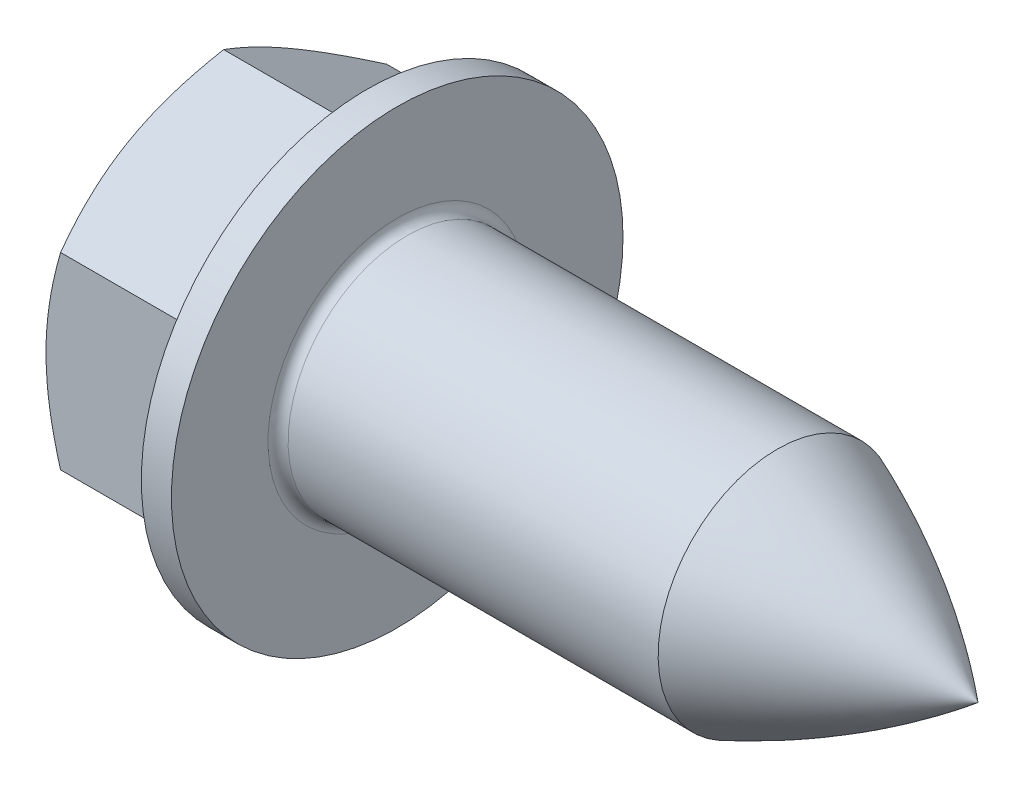
SolidWorks part; units mm, degrees
ref_plane "Front" through (0, 0, 0) normal (0, 0, 1) x (1, 0, 0)
ref_plane "Top" through (0, 0, 0) normal (0, 1, 0) x (1, 0, 0)
ref_plane "Right" through (0, 0, 0) normal (1, 0, 0) x (0, 0, -1)
sketch "Sketch2" plane through (0, 0, 0) normal (1, 0, 0) x (0, 0, -1)
  line L1 (0, 7.5056) -> (-6.5, 3.7528)
  line L2 (-6.5, 3.7528) -> (-6.5, -3.7528)
  line L3 (-6.5, -3.7528) -> (0, -7.5056)
  line L4 (0, -7.5056) -> (6.5, -3.7528)
  line L5 (6.5, -3.7528) -> (6.5, 3.7528)
  line L6 (6.5, 3.7528) -> (0, 7.5056)
  circle A0 centre (0, 0) radius 6.5 construction
extrude "BaseHead" add sketch "Sketch2" along normal blind 7.5
sketch "Sketch1" plane through (0, 0, 0) normal (0, 0, 1) x (1, 0, 0)
  line L0 (-9.5445, 0) -> (41.9665, 0) construction
  line L1 (30.65, 0) -> (30.65, 4.75)
  line L2 (30.65, 4.75) -> (7.5, 4.75)
  line L3 (7.5, 4.75) -> (7.5, 0)
  line L4 (30.65, 0) -> (7.5, 0)
  line L5 (7.5, 3.7528) -> (7.5, -3.7528) construction
  line L6 (9.6, 7.9501) -> (9.6, -3.7754) construction
  dimension "l" = 23.15
revolve "BaseBody" add sketch "Sketch1" angle 360 about L0
cosmetic thread "ThreadCosmetic1" [suppressed] parameters "D1"=21.05, "D2"=8.5
sketch "Sketch3" plane through (7.5, -3.7817, 4.2127) normal (1, 0, 0) x (0, 0, -1)
  circle A0 centre (4.2127, 3.7817) radius 9
  dimension "dc" = 18
extrude "Neck" add sketch "Sketch3" against normal blind 1.2
sketch "Sketch4" plane through (0, 0, 0) normal (0, 0, 1) x (1, 0, 0)
  line L0 (10.6638, 0) -> (-1.5125, 0) construction
  line L2 (0, 6.5) -> (0.5806, 7.5056)
  line L5 (0.5806, 7.5056) -> (0, 7.5056)
  line L6 (0, 7.5056) -> (0, 6.5)
  dimension "D1" = 13
  dimension "D2" = 30
revolve "Cut-Revolve7" cut sketch "Sketch4" angle 360 about L0
fillet "Fillet1" radius 0.4 1 edges at (7.5, 0, 4.75)
fillet "Fillet2" radius 0.6 6 edges at (6.3, -5.6292, -3.25) (6.3, -5.6292, 3.25) (6.3, 0, 6.5) (6.3, 5.6292, 3.25) (6.3, 5.6292, -3.25) (6.3, 0, -6.5)
sketch "Sketch5" plane through (0, 0, 0) normal (0, 0, 1) x (1, 0, 0)
  line L0 (31.9782, 0) -> (17.0112, 0) construction
  line L2 (26.45, -4.75) -> (28.55, -4.75)
  line L3 (28.55, -4.75) -> (30.65, -4.225)
  line L5 (30.65, -4.75) -> (30.65, 4.75) construction
  line L6 (26.45, -4.75) -> (26.45, -5.25)
  line L7 (26.45, -5.25) -> (30.65, -5.25)
  line L8 (30.65, -5.25) -> (30.65, -4.225)
  point P15 (28.55, -4.75)
  dimension "D2" = 2.1
  dimension "D4" = 0.5
  dimension "D1" = 9.5
  dimension "D3" = 0.525
revolve "Cut-Revolve1" cut sketch "Sketch5" angle 360 about L0
sketch "Sketch6" plane through (0, 0, 0) normal (0, 0, 1) x (1, 0, 0)
  line L0 (33.3907, 0) -> (10.0621, 0) construction
  line L2 (30.65, -4.75) -> (30.65, 4.75) construction
  line L3 (30.65, 0) -> (22.65, -4.75) construction
  line L6 (30.65, 0) -> (31.15, 0)
  line L7 (22.65, -4.75) -> (30.65, -4.75)
  line L8 (31.15, 0) -> (31.15, -4.75)
  line L9 (31.15, -4.75) -> (30.65, -4.75)
  arc A0 (30.65, 0) -> (22.65, -4.75) centre (10.4863, 24.8481) cw
  dimension "D1" = 32
  dimension "D3" = 9.5
  dimension "D2" = 0.5
revolve "Cut-Revolve6" cut sketch "Sketch6" angle 360 about L0
sketch "Sketch7" plane through (0, 0, 0) normal (0, 0, 1) x (1, 0, 0)
  line L0 (0, 0) -> (-5.4653, 0) construction
  line L1 (-0.1, 5.4167) -> (0.9, 5.4167)
  line L2 (-0.1, 5.4167) -> (-0.1, 0)
  line L3 (-0.1, 0) -> (1.15, 0)
  line L4 (1.15, 5.1667) -> (1.15, 0)
  arc A0 (0.9, 5.4167) -> (1.15, 5.1667) centre (0.9, 5.1667) cw
  point P9 (1.15, 5.4167)
  dimension "D4" = 0.25
  dimension "D1" = 0.1
  dimension "D2" = 10.8333
  dimension "D3" = 1.25
revolve "Cut-Revolve8" cut sketch "Sketch7" angle 360 about L0
sketch "Sketch8" plane through (0, 0, 0) normal (0, 0, 1) x (1, 0, 0)
  line L0 (9.35, 5.25) -> (9.85, 5.25)
  line L1 (9.85, 5.25) -> (9.85, 4.75)
  line L2 (9.85, 4.75) -> (9.6, 4.317)
  line L3 (9.6, 4.317) -> (9.35, 4.75)
  line L4 (9.35, 4.75) -> (9.35, 5.25)
  line L5 (0, 0) -> (32.2552, 0) construction
  line L6 (7.5, -9) -> (7.5, 9) construction
  dimension "D1" = 9.5
  dimension "D2" = 0.5
  dimension "D3" = 2.1
revolve "Cut-Revolve10" [suppressed] cut sketch "Sketch8" angle 360 about L5
pattern_linear "LPattern10" [suppressed] count 35 spacing 0.6 along (1, 0, 0) of bodies 108
equation "\"D3@Sketch5\" = \"yf@Sketch5\" / 8"
equation "\"D2@ThreadCosmetic1\" = \"st@Sketch1\" - 1"
equation "\"D1@Sketch6\" = \"yc@Sketch6\" * 4"
equation "\"D3@Sketch6\" = \"st@Sketch1\""
equation "\"D2@Sketch5\" = \"yf@Sketch5\" / 2"
equation "\"D1@Sketch4\" = \"s@Sketch2\""
equation "\"D1@Sketch5\" = \"st@Sketch1\""
equation "\"D1@ThreadCosmetic1\" = \"l@Sketch1\" - \"a@Sketch1\""
equation "\"D2@Sketch7\" = \"s@Sketch2\" * 5 / 6"
equation "\"D3@Sketch7\" = \"k@BaseHead\" / 6"
equation "\"D4@Sketch7\" = \"D3@Sketch7\" / 5"
equation "\"D1@Sketch8\" = \"st@Sketch1\""
equation "\"D2@Sketch8\" =  ( \"st@Sketch1\" - \"D2@ThreadCosmetic1\" )  / 2"
equation "\"D3@Sketch8\" = \"a@Sketch1\""
equation "\"D3@LPattern10\" = \"D2@Sketch8\" * 1.2"
equation "\"D1@LPattern10\" = \"D1@ThreadCosmetic1\" / \"D3@LPattern10\""
